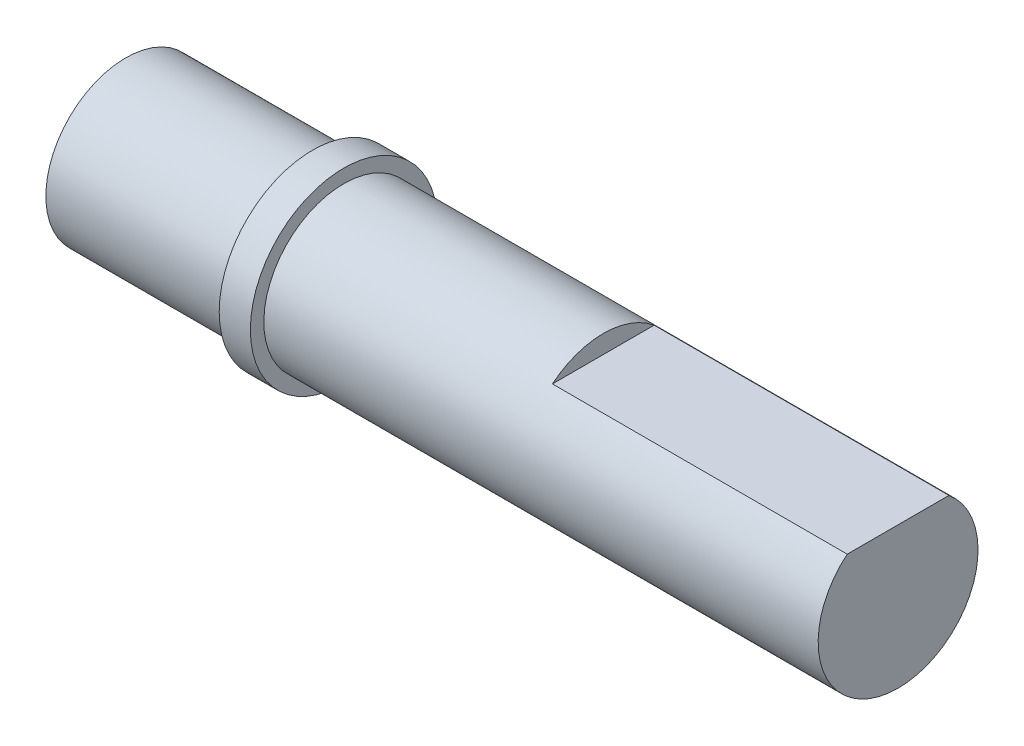
SolidWorks part; units mm, degrees
ref_plane "Front Plane" through (0, 0, 0) normal (0, 0, 1) x (1, 0, 0)
ref_plane "Top Plane" through (0, 0, 0) normal (0, 1, 0) x (1, 0, 0)
ref_plane "Right Plane" through (0, 0, 0) normal (1, 0, 0) x (0, 0, -1)
sketch "Sketch9" plane through (0, 0, 0) normal (1, 0, 0) x (0, 0, -1)
  line L0 (-2.45, 2.9698) -> (2.45, 2.9698)
  circle A0 centre (0, 0) radius 4.5
  circle A1 centre (0, 0) radius 3.85
  point P6 (0, 0)
  dimension "D1" = 4.9
  dimension "D2" = 7.7
  dimension "D3" = 9
extrude "Boss-Extrude1" add sketch "Sketch9" along normal blind 28.2 contours L0 A1 region at (0, -0.2248, 0)
extrude "Boss-Extrude2" add sketch "Sketch9<6>" along normal blind 1.5 contours A0 A1 region at (0, 0, 4.3727)
sketch "Sketch9<6>" plane through (0, 0, 0) normal (1, 0, 0) x (0, 0, -1) same geometry as "Sketch9"
extrude "Boss-Extrude3" add sketch "Sketch9<7>" along normal blind 14 contours L0 A1 region at (0, 3.3256, 0)
sketch "Sketch9<7>" plane through (0, 0, 0) normal (1, 0, 0) x (0, 0, -1) same geometry as "Sketch9"
extrude "Boss-Extrude4" add sketch "Sketch9<8>" against normal blind 9 contours L0 A1 | L0 A1 region at (0, 3.3256, 0) region at (0, -0.2248, 0)
sketch "Sketch9<8>" plane through (0, 0, 0) normal (1, 0, 0) x (0, 0, -1) same geometry as "Sketch9"
